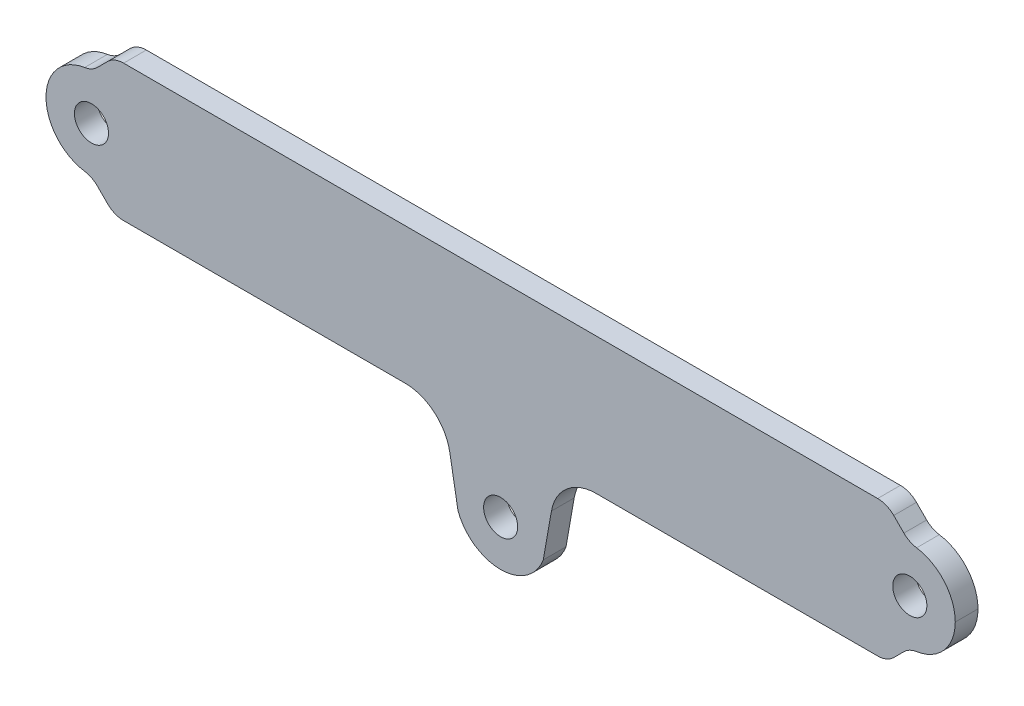
SolidWorks part; units mm, degrees
ref_plane "Front Plane" through (0, 0, 0) normal (0, 0, 1) x (1, 0, 0)
ref_plane "Top Plane" through (0, 0, 0) normal (0, 1, 0) x (1, 0, 0)
ref_plane "Right Plane" through (0, 0, 0) normal (1, 0, 0) x (0, 0, -1)
sketch "Sketch1" plane through (0, 0, 0) normal (0, 0, 1) x (1, 0, 0)
  line L10 (5.08, 10.16) -> (7.62, 12.7)
  line L11 (0, 0) -> (5.08, 0)
  line L12 (0, 0) -> (0, 10.16)
  line L13 (0, 10.16) -> (5.08, 10.16)
  line L15 (7.62, 12.7) -> (50.8, 12.7)
  line L17 (5.08, 0) -> (7.62, -2.54)
  line L18 (7.62, -2.54) -> (44.3811, -2.54)
  line L22 (50.8, -2.54) -> (50.8, 12.7)
  line L23 (44.3811, -2.54) -> (46.0354, -11.9221)
  line L24 (50.8, -15.24) -> (50.8, -12.065)
  line L25 (50.8, -8.255) -> (50.8, -2.54)
  circle A0 centre (5.08, 5.08) radius 1.905
  arc A2 (46.0354, -11.9221) -> (50.8, -15.24) centre (50.8, -10.16) ccw
  arc A3 (50.8, -8.255) -> (50.8, -12.065) centre (50.8, -10.16) ccw
  dimension "D11" = 5.08
  dimension "D13" = 3.81
  dimension "D14" = 7.62
  dimension "D18" = 1.905
  dimension "D2" = 10.16
  dimension "D3" = 45
  dimension "D4" = 80
  dimension "D5" = 5.08
  dimension "D6" = 50.8
  dimension "D7" = 45
  dimension "D9" = 2.54
  dimension "D10" = 2.54
  dimension "D12" = 5.08
  dimension "D15" = 50.8
  dimension "D16" = 5.08
  dimension "D17" = 5.08
extrude "Boss-Extrude1" add sketch "Sketch1" along normal blind 2.54
fillet "Fillet5" radius 5.08 3 edges at (44.3811, -2.54, 1.27) (0, 0, 1.27) (0, 10.16, 1.27)
fillet "Fillet6" radius 2.54 4 edges at (7.62, -2.54, 1.27) (5.08, 0, 1.27) (5.08, 10.16, 1.27) (7.62, 12.7, 1.27)
mirror "Mirror5" about plane through (50.8, -2.54, 2.54) normal (-1, 0, 0) of bodies 101
